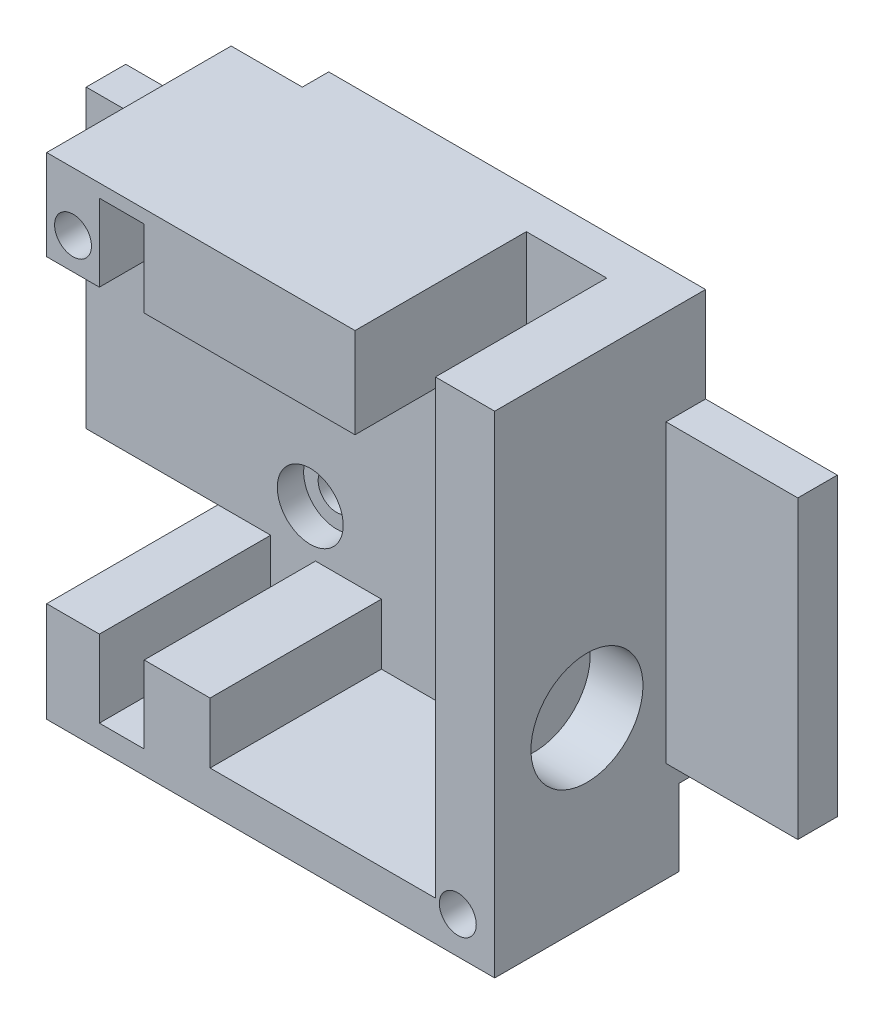
SolidWorks part; units mm, degrees
ref_plane "Front Plane" through (0, 0, 0) normal (0, 0, 1) x (1, 0, 0)
ref_plane "Top Plane" through (0, 0, 0) normal (0, 1, 0) x (1, 0, 0)
ref_plane "Right Plane" through (0, 0, 0) normal (1, 0, 0) x (0, 0, -1)
sketch "Sketch1" plane through (0, 0, 0) normal (0, 0, 1) x (1, 0, 0)
  line L1 (-17, 19) -> (17, 19)
  line L2 (-17, 19) -> (-17, -19)
  line L3 (-17, -19) -> (17, -19)
  line L4 (17, 19) -> (17, -19)
  line L5 (-17, 19) -> (17, -19) construction
  line L6 (-17, -19) -> (17, 19) construction
  point P0 (0, 0)
  dimension "D1" = 38
  dimension "D2" = 34
extrude "Boss-Extrude1" add sketch "Sketch1" along normal blind 16
sketch "Sketch2" plane through (0, 0, 16) normal (0, 0, 1) x (1, 0, 0)
  line L0 (0, 0) -> (-17, 0) construction
  line L5 (-17, 11.4) -> (5.4, 11.4)
  line L6 (-17, 11.4) -> (-17, -11.4)
  line L7 (-17, -11.4) -> (5.4, -11.4)
  line L8 (5.4, 11.4) -> (5.4, -11.4)
  line L9 (-17, 11.4) -> (5.4, -11.4) construction
  line L10 (-17, -11.4) -> (5.4, 11.4) construction
  line L11 (-17, 19) -> (-17, -19) construction
  line L12 (-10.6, -11.4) -> (-10.6, -16.25)
  line L13 (-13, 11.4) -> (-10.6, 11.4)
  line L14 (-13, 11.4) -> (-13, 16.25)
  line L15 (-13, 16.25) -> (-10.6, 16.25)
  line L16 (-10.6, 11.4) -> (-10.6, 16.25)
  line L17 (-13, -11.4) -> (-13, -16.25)
  line L18 (-13, -16.25) -> (-10.6, -16.25)
  line L21 (-17, -11.4) -> (-17, 4.4)
  point P0 (-5.8, 0)
  dimension "D1" = 22.4
  dimension "D2" = 22.8
  dimension "D3" = 5.8
  dimension "D4" = 4
  dimension "D5" = 2.4
  dimension "D6" = 4.85
extrude "Cut-Extrude1" cut sketch "Sketch2" against normal blind 13 contours L8 L5 L6 L7 | L17 L18 L12 L7 | L5 L16 L15 L14
sketch "Sketch3" plane through (0, 0, 16) normal (0, 0, 1) x (1, 0, 0)
  line L1 (5.4, -11.4) -> (-4.6, -11.4)
  line L2 (5.4, -11.4) -> (5.4, -16)
  line L3 (5.4, -16) -> (-4.6, -16)
  line L4 (-4.6, -11.4) -> (-4.6, -16)
  line L5 (5.4, -16) -> (8.4, -16)
  line L6 (5.4, -16) -> (5.4, -11.4)
  line L7 (5.4, -11.4) -> (8.4, -11.4)
  line L8 (8.4, -16) -> (8.4, -11.4)
  line L10 (-17, -19) -> (17, -19) construction
  line L11 (17, 19) -> (-17, 19) construction
  line L12 (8.4, -16) -> (11.4, -16)
  line L13 (8.4, -16) -> (8.4, 19)
  line L14 (8.4, 19) -> (11.4, 19)
  line L15 (11.4, -16) -> (11.4, 19)
  line M11 (17, 19) -> (-17, 19)
  line M21 (5.4, -11.4) -> (-10.6, -11.4)
  dimension "D1" = 3
  dimension "D2" = 10
  dimension "D3" = 3
  dimension "D4" = 3
extrude "Cut-Extrude2" cut sketch "Sketch3" against normal blind 13 contours L12 L15 L13 L8 M11 | L4 L3 L2 M21 | L5 L8 L7 L2 region at (0.4, -13.7, 16) region at (6.9, -13.7, 16) region at (9.9, 1.5, 16)
sketch "Sketch4" plane through (0, 0, 16) normal (0, 0, 1) x (1, 0, 0)
  line L0 (-17, 19) -> (-17, 11.4) construction
  line L3 (-17, -19) -> (17, -19) construction
  line L4 (17, -19) -> (17, 19) construction
  line L5 (8.4, 19) -> (-17, 19) construction
  circle A0 centre (-15, 13.8) radius 1.4
  circle A1 centre (14.2, -16.2) radius 1.4
  dimension "D2" = 5.2
  dimension "D3" = 2.8
  dimension "D4" = 2.8
  dimension "D5" = 2.8
  dimension "D6" = 2.8
  dimension "D1" = 2
extrude "Cut-Extrude3" cut sketch "Sketch4" against normal through all
sketch "Sketch5" plane through (0, 0, 0) normal (0, 0, -1) x (-1, 0, 0)
  line L0 (-17, 19) -> (17, 19) construction
  line L1 (18.4, 13.8) -> (11.6, 13.8)
  line L2 (18.4, 13.8) -> (18.4, 19)
  line L3 (18.4, 19) -> (11.6, 19)
  line L4 (11.6, 13.8) -> (11.6, 19)
  line L5 (-17, -19) -> (-17, 19) construction
  line L6 (-14.2, -19.2) -> (-17, -19.2)
  line L7 (-14.2, -19.2) -> (-14.2, -13.2)
  line L8 (-14.2, -13.2) -> (-17, -13.2)
  line L9 (-17, -19.2) -> (-17, -13.2)
  line L11 (-14.2, -19.2) -> (-10.2, -19.2)
  line L12 (-14.2, -19.2) -> (-14.2, -13.2)
  line L13 (-14.2, -13.2) -> (-10.2, -13.2)
  line L14 (-10.2, -19.2) -> (-10.2, -13.2)
  circle A0 centre (15, 13.8) radius 3.4
  circle A1 centre (-14.2, -16.2) radius 3
  circle M1 centre (15, 13.8) radius 1.4
  circle M2 centre (-14.2, -16.2) radius 1.4
  line M3 (-17, 19) -> (-17, -19)
  line M4 (-17, -19) -> (17, -19)
  line M5 (17, -19) -> (17, 19)
  line M6 (17, 19) -> (-17, 19)
  dimension "D1" = 6.8
  dimension "D2" = 6
  dimension "D3" = 4
extrude "Cut-Extrude5" cut sketch "Sketch5" against normal blind 2 contours A1 L7 M4 M2 | L7 A1 L9 M4 M2 | A1 M3 M4 | A1 L8 M3 | L9 A1 | A1 L7 M4 | A1 L9 L6 M4 | L7 A1 M4 | A0 L2 L3 M5 | A0 L4 M5 M6 | A0 L1 M5 M1 | L1 A0 M5 | A0 L1 M5 | L1 A0 M5 M1 | A1 L14 L13 M4 region at (-17.5712, 12.7332, 0) region at (-17.7757, 17.3011, 0) region at (-17.5712, 14.8668, 0) region at (-14.4405, 12.0641, 0) region at (-14.4405, 15.5359, 0) region at (-13.9912, 17.7377, 0) region at (11.1092, -15.9933, 0) region at (12.7237, -16.1618, 0) region at (13.7943, -19.0802, 0) region at (16.3521, -13.7212, 0) region at (14.6057, -19.0802, 0) region at (15.9461, -19.1069, 0) region at (15.6381, -16.1608, 0) region at (17.0802, -16.2, 0) region at (16.5111, -18.5111, 0)
sketch "Sketch7" plane through (0, 19, 0) normal (0, 1, 0) x (1, 0, 0)
  line L0 (17, -16) -> (17, 0) construction
  line L1 (-17, -16) -> (17, -16)
  line L2 (-17, -16) -> (-17, -15)
  line L3 (-17, -15) -> (17, -15)
  line L4 (17, -16) -> (17, -15)
  dimension "D1" = 1
extrude "Cut-Extrude6" cut sketch "Sketch7" against normal through all
sketch "Sketch9" plane through (0, 0, 15) normal (0, 0, 1) x (1, 0, 0)
  line L0 (8.4, 19) -> (-17, 19) construction
  line L1 (-9, 19) -> (17, 19)
  line L2 (-9, 19) -> (-9, 12.5)
  line L3 (-9, 12.5) -> (17, 12.5)
  line L4 (17, 19) -> (17, 12.5)
  line L5 (17, -19) -> (17, 19) construction
  line L6 (-17, -19) -> (-17, -11.4) construction
  line L7 (-17, -12.4) -> (-14, -12.4)
  line L8 (-17, -12.4) -> (-17, -19)
  line L9 (-17, -19) -> (-14, -19)
  line L10 (-14, -12.4) -> (-14, -19)
  line L11 (17, -19) -> (-17, -19) construction
  line L12 (-13, -16.25) -> (-10.6, -16.25) construction
  line L13 (-8.6, -19) -> (-5.6, -19)
  line L14 (-8.6, -19) -> (-8.6, -12.4)
  line L15 (-8.6, -12.4) -> (-5.6, -12.4)
  line L16 (-5.6, -19) -> (-5.6, -12.4)
  line L17 (-5.6, -19) -> (11.4, -19)
  line L18 (-5.6, -19) -> (-5.6, -17)
  line L19 (-5.6, -17) -> (11.4, -17)
  line L20 (11.4, -19) -> (11.4, -17)
  line L21 (-14, -19) -> (-8.6, -19)
  line L22 (-14, -19) -> (-14, -18.25)
  line L23 (-10.6, -11.4) -> (-4.6, -11.4) construction
  line L24 (-17, -11.4) -> (-13, -11.4) construction
  line L25 (-10.6, -11.4) -> (-10.6, -16.25) construction
  line L26 (-4.6, -11.4) -> (-4.6, -16) construction
  line L27 (-4.6, -16) -> (11.4, -16) construction
  line L28 (-13, -11.4) -> (-13, -16.25) construction
  line L29 (-14, -18.25) -> (-8.6, -18.25)
  line L30 (-8.6, -19) -> (-8.6, -18.25)
  line L32 (-13, 16.25) -> (-10.6, 16.25) construction
  line L33 (-17, 19) -> (-9, 19)
  line L34 (-17, 19) -> (-17, 18.25)
  line L35 (-17, 18.25) -> (-9, 18.25)
  line L36 (-9, 19) -> (-9, 18.25)
  line L37 (11.4, -16) -> (11.4, 19) construction
  line L38 (17, 19) -> (13.4, 19)
  line L39 (17, 19) -> (17, 1)
  line L40 (17, 1) -> (13.4, 1)
  line L41 (13.4, 19) -> (13.4, 1)
  line M21 (8.4, -11.4) -> (8.4, 19)
  line M22 (8.4, 19) -> (-17, 19)
  line M23 (-17, 19) -> (-17, 11.4)
  dimension "D1" = 6.5
  dimension "D2" = 26
  dimension "D3" = 1
  dimension "D4" = 1
  dimension "D5" = 2
  dimension "D6" = 1
  dimension "D7" = 1
  dimension "D8" = 1
  dimension "D9" = 2
  dimension "D10" = 2
  dimension "D11" = 2
  dimension "D12" = 17
  dimension "D13" = 18
extrude "Cut-Extrude9" cut sketch "Sketch9" against normal through all contours L2 L3 M21 M22 | L35 L2 M23 M22 | L41 L1 L3 M21 | L1 L41 L3 L4 | L3 L41 L40 L39 | L17 L20 L19 L16 | L13 L16 L15 L14 | L29 L10 L21 L14 | L10 L7 L8 L9 region at (-0.3, 15.75, 15) region at (-13, 18.625, 15) region at (10.9, 15.75, 15) region at (15.2, 15.75, 15) region at (15.2, 6.75, 15) region at (-15.5, -15.7, 15) region at (-11.3, -18.625, 15) region at (-7.1, -15.7, 15) region at (2.9, -18, 15)
sketch "Sketch10" plane through (0, 0, 3) normal (0, 0, 1) x (1, 0, 0)
  line L1 (-10, 8) -> (10, 8)
  line L2 (-10, 8) -> (-10, -8)
  line L3 (-10, -8) -> (10, -8)
  line L4 (10, 8) -> (10, -8)
  line L5 (-10, 8) -> (10, -8) construction
  line L6 (-10, -8) -> (10, 8) construction
  circle A0 centre (-10, 8) radius 2.5
  circle A1 centre (10, 8) radius 2.5
  circle A2 centre (-10, -8) radius 2.5
  circle A3 centre (10, -8) radius 2.5
  point P0 (0, 0)
  line M6 (8.4, 12.5) -> (8.4, -11.4)
  line M22 (11.4, -16) -> (11.4, 12.5)
  dimension "D3" = 5
  dimension "D1" = 20
  dimension "D2" = 16
extrude "Cut-Extrude10" cut sketch "Sketch10" against normal blind 2 and the other way through all contours L2 A0 L1 | L1 A0 L2 | A1 L4 L1 M6 | A1 L1 L4 M22 M6 | A1 M22 | A1 L1 M6 | L1 A1 M6 | L3 A2 L2 | L2 A2 L3 | A3 L4 L3 M22 M6 | A3 M22 | L4 A3 L3 M6 | A3 L3 M6 | L3 A3 M6 region at (-10.3537, 8.3537, 3) region at (-8.939, 6.939, 3) region at (8.0338, 8.7415, 3) region at (8.0338, 7.2585, 3) region at (-8.939, -6.939, 3) region at (-10.3537, -8.3537, 3) region at (10.1596, 8.4183, 3) region at (9.2324, 6.8354, 3) region at (11.8495, 8, 3) region at (8.0338, -7.2585, 3) region at (9.2324, -6.8354, 3) region at (8.0338, -8.7415, 3) region at (10.1596, -8.4183, 3) region at (11.8495, -8, 3)
sketch "Sketch11" plane through (0, 0, 15) normal (0, 0, 1) x (1, 0, 0)
  line L5 (5.4, -11.4) -> (8.4, -11.4) construction
  line L6 (12.5, -8) -> (7.5, -8)
  line L7 (12.5, -8) -> (12.5, -11.4)
  line L8 (11.4, -11.4) -> (7.5, -11.4)
  line L9 (7.5, -8) -> (7.5, -11.4)
  line L10 (-9, 12.5) -> (8.4, 12.5) construction
  line L11 (12.5, 8) -> (7.5, 8)
  line L12 (12.5, 8) -> (12.5, 12.5)
  line L13 (12.5, 12.5) -> (7.5, 12.5)
  line L14 (7.5, 8) -> (7.5, 12.5)
  line L16 (11.4, -16) -> (12.5, -16)
  line L17 (11.4, -16) -> (11.4, -11.4)
  line L19 (12.5, -16) -> (12.5, -11.4)
  arc A0 (11.4, -10.0712) -> (11.4, -5.9288) centre (10, -8) ccw construction
  arc A1 (11.4, 5.9288) -> (11.4, 10.0712) centre (10, 8) ccw construction
extrude "Cut-Extrude11" cut sketch "Sketch11" against normal blind 12
sketch "Sketch12" plane through (0, 0, 15) normal (0, 0, 1) x (1, 0, 0)
  line L1 (-10.6, 11.4) -> (-9.6, 11.4)
  line L2 (-10.6, 11.4) -> (-10.6, 16.25)
  line L3 (-10.6, 16.25) -> (-9.6, 16.25)
  line L4 (-9.6, 11.4) -> (-9.6, 16.25)
  line L5 (-10.6, -11.4) -> (-9.6, -11.4)
  line L6 (-10.6, -11.4) -> (-10.6, -16.25)
  line L7 (-10.6, -16.25) -> (-9.6, -16.25)
  line L8 (-9.6, -11.4) -> (-9.6, -16.25)
  line L10 (5.4, -11.4) -> (6.4, -11.4)
  line L11 (5.4, -11.4) -> (5.4, 11.4)
  line L12 (5.4, 11.4) -> (6.4, 11.4)
  line L13 (6.4, -11.4) -> (6.4, 11.4)
  dimension "D1" = 1
  dimension "D2" = 1
  dimension "D3" = 4.85
  dimension "D4" = 4.85
  dimension "D5" = 1
extrude "Cut-Extrude12" cut sketch "Sketch12" against normal blind 12
sketch "Sketch14" plane through (17, 0, 0) normal (1, 0, 0) x (0, 0, -1)
  line L0 (-15, -19) -> (-15, 1) construction
  line L1 (-15, -19) -> (-2, -19) construction
  circle A0 centre (-9, -5.4) radius 4.25
  dimension "D1" = 8.5
  dimension "D2" = 6
  dimension "D3" = 13.6
extrude "Cut-Extrude13" cut sketch "Sketch14" against normal blind 4
sketch "Sketch17" plane through (0, 0, 15) normal (0, 0, 1) x (1, 0, 0)
  line L1 (-13, 16.25) -> (-9.6, 16.25)
  line L2 (-13, 16.25) -> (-13, 17.25)
  line L3 (-13, 17.25) -> (-9.6, 17.25)
  line L4 (-9.6, 16.25) -> (-9.6, 17.25)
  line L7 (-9.6, -16.25) -> (-13, -16.25)
  line L8 (-9.6, -16.25) -> (-9.6, -17.25)
  line L9 (-9.6, -17.25) -> (-13, -17.25)
  line L10 (-13, -16.25) -> (-13, -17.25)
  dimension "D1" = 1
  dimension "D2" = 3.4
  dimension "D3" = 1
  dimension "D4" = 3.4
extrude "Cut-Extrude16" cut sketch "Sketch17" against normal blind 12
sketch "Sketch18" plane through (0, 0, 1) normal (0, 0, 1) x (1, 0, 0)
  circle A1 centre (-10, 8) radius 1.4
  circle A2 centre (10, 8) radius 1.4
  circle A3 centre (-10, -8) radius 1.4
  circle A4 centre (10, -8) radius 1.4
  dimension "D1" = 2.8
  dimension "D2" = 2.8
  dimension "D3" = 2.8
  dimension "D4" = 2.8
extrude "Cut-Extrude17" cut sketch "Sketch18" against normal blind 12
sketch "Sketch19" plane through (0, 0, 0) normal (0, 0, 1) x (1, 0, 0)
  line L1 (-17, 18.25) -> (17, 18.25)
  line L2 (-17, 18.25) -> (-17, -19)
  line L3 (-17, -19) -> (17, -19)
  line L4 (17, 18.25) -> (17, -19)
  line L5 (-9, 18.25) -> (17, 18.25)
  line L6 (-9, 18.25) -> (-9, 12.4767)
  line L7 (-9, 12.4767) -> (17, 12.4767)
  line L8 (17, 18.25) -> (17, 12.4767)
  line L9 (17, 12.4767) -> (13.4, 12.4767)
  line L10 (17, 12.4767) -> (17, 1)
  line L11 (17, 1) -> (13.4, 1)
  line L12 (13.4, 12.4767) -> (13.4, 1)
  line L13 (-17, -12.4) -> (-14, -12.4)
  line L14 (-17, -12.4) -> (-17, -19)
  line L15 (-17, -19) -> (-14, -19)
  line L16 (-14, -12.4) -> (-14, -19)
  line L17 (-14, -19) -> (-8.6, -19)
  line L18 (-14, -19) -> (-14, -18.25)
  line L19 (-14, -18.25) -> (-8.6, -18.25)
  line L20 (-8.6, -19) -> (-8.6, -18.25)
  line L21 (-8.6, -12.4) -> (-5.6, -12.4)
  line L22 (-8.6, -12.4) -> (-8.6, -19)
  line L23 (-8.6, -19) -> (-5.6, -19)
  line L24 (-5.6, -12.4) -> (-5.6, -19)
  line L25 (-5.6, -17) -> (11.4, -17)
  line L26 (-5.6, -17) -> (-5.6, -19)
  line L27 (-5.6, -19) -> (11.4, -19)
  line L28 (11.4, -17) -> (11.4, -19)
extrude "Boss-Extrude2" add sketch "Sketch19" along normal blind 16 contours L6 L7 L4 L1 | L7 L12 L11 L4 | L24 L21 L22 L20 L3 | L16 L13 L2 L3 | L3 L20 L19 L16 | L28 L25 L24 L3 region at (4, 15.3633, 0) region at (-15.5, -15.7, 0) region at (15.2, 6.7383, 0) region at (-11.3, -18.625, 0) region at (-7.1, -15.7, 0) region at (2.9, -18, 0)
sketch "Sketch20" plane through (0, 0, 15) normal (0, 0, 1) x (1, 0, 0)
  line L0 (-9.6, 11.4) -> (6.4, 11.4) construction
  line L1 (-17, 18.25) -> (17, 18.25)
  line L2 (-17, 18.25) -> (-17, -19)
  line L3 (-17, -19) -> (17, -19)
  line L4 (17, 18.25) -> (17, -19)
  line L5 (-13, 11.4) -> (-17, 11.4)
  line L6 (-13, 11.4) -> (-13, 18.25)
  line L7 (-13, 18.25) -> (-17, 18.25)
  line L8 (-17, 11.4) -> (-17, 18.25)
  line L9 (-13, 18.25) -> (-9.6, 18.25)
  line L10 (-13, 18.25) -> (-13, 17.25)
  line L11 (-13, 17.25) -> (-9.6, 17.25)
  line L12 (-9.6, 18.25) -> (-9.6, 17.25)
  line L13 (-9.6, 18.25) -> (-9, 18.25)
  line L14 (-9.6, 18.25) -> (-9.6, 11.4)
  line L15 (-9.6, 11.4) -> (-9, 11.4)
  line L16 (-9, 18.25) -> (-9, 11.4)
  line L17 (-17, -11.4) -> (-13, -11.4)
  line L18 (-9, 11.4) -> (7.5, 11.4)
  line L19 (-9, 11.4) -> (-9, 12.4767)
  line L20 (-9, 12.4767) -> (7.5, 12.4767)
  line L21 (7.5, 11.4) -> (7.5, 12.4767)
  line L22 (7.5, -11.4) -> (6.4, -11.4)
  line L23 (7.5, -11.4) -> (7.5, 11.4)
  line L24 (7.5, 11.4) -> (6.4, 11.4)
  line L25 (6.4, -11.4) -> (6.4, 11.4)
  line L26 (17, -19) -> (13.4, -19)
  line L27 (17, -19) -> (17, 1)
  line L28 (17, 1) -> (13.4, 1)
  line L30 (-13, -11.4) -> (-13, -17.25)
  line L31 (-13, -17.25) -> (-9.6, -17.25)
  line L32 (-9.6, -17.25) -> (-9.6, -11.4)
  line L33 (-9.6, -11.4) -> (-4.6, -11.4)
  line L34 (-4.6, -11.4) -> (-4.6, -16)
  line L35 (-4.6, -16) -> (12.5, -16)
  line L36 (12.5, -16) -> (12.5, 12.4767)
  line L37 (12.5, 12.4767) -> (13.4, 12.4767)
  line L38 (13.4, 12.4767) -> (13.4, 1)
  line L39 (-17, -12.4) -> (-14, -12.4)
  line L40 (-14, -12.4) -> (-14, -18.25)
  line L41 (-14, -18.25) -> (-8.6, -18.25)
  line L42 (-8.6, -18.25) -> (-8.6, -12.4)
  line L43 (-8.6, -12.4) -> (-5.6, -12.4)
  line L44 (-5.6, -12.4) -> (-5.6, -17)
  line L45 (-5.6, -17) -> (11.4, -17)
  line L46 (11.4, -17) -> (11.4, -19)
  line L47 (11.4, -19) -> (17, -19)
  circle A0 centre (-15, 13.8) radius 1.4
  circle A1 centre (14.2, -16.2) radius 1.4
  circle M5 centre (-15, 13.8) radius 1.4
  line M6 (7.5, 12.4767) -> (-9, 12.4767)
  line M7 (-9, 12.4767) -> (-9, 18.25)
  line M8 (-9, 18.25) -> (-17, 18.25)
  line M9 (-17, 18.25) -> (-17, 11.4)
  line M10 (-17, 11.4) -> (-13, 11.4)
  line M11 (-13, 11.4) -> (-13, 17.25)
  line M12 (-13, 17.25) -> (-9.6, 17.25)
  line M13 (-9.6, 17.25) -> (-9.6, 11.4)
  line M14 (-9.6, 11.4) -> (6.4, 11.4)
  line M15 (6.4, 11.4) -> (6.4, -11.4)
  line M16 (6.4, -11.4) -> (7.5, -11.4)
  line M17 (7.5, -11.4) -> (7.5, -8)
  line M21 (7.5, 8) -> (7.5, 12.4767)
extrude "Boss-Extrude3" add sketch "Sketch20" along normal blind 1 contours L6 L1 M11 M9 M10 M5 | L12 L1 L6 M12 | L16 L12 M7 M8 M13 M14 | L18 L16 M14 M21 M6 | L23 L18 M17 M21 M15 M16 | L45 L46 L3 L4 L28 L38 L37 L36 L35 L34 L33 L32 L31 L30 L17 L2 L39 L40 L41 L42 L43 L44 A1 region at (-15, 18.1707, 15) region at (-11.3, 17.75, 15) region at (-9.3, 14.825, 15) region at (-15, -11.8633, 15) region at (-0.75, 11.9383, 15) region at (6.95, 0, 15)
sketch "Sketch21" plane through (0, 0, 16) normal (0, 0, 1) x (1, 0, 0)
  line L0 (12.5, -16) -> (12.5, -8) construction
  line L1 (7.5, 12.4767) -> (6.4, 12.4767)
  line L2 (7.5, 12.4767) -> (7.5, -11.4)
  line L3 (7.5, -11.4) -> (6.4, -11.4)
  line L4 (6.4, 12.4767) -> (6.4, -11.4)
  line L5 (7.5, 12.4767) -> (12.5, 12.4767)
  line L6 (7.5, 12.4767) -> (7.5, -11.4)
  line L7 (7.5, -11.4) -> (12.5, -11.4)
  line L8 (12.5, 12.4767) -> (12.5, -11.4)
  line M13 (6.4, 11.4) -> (6.4, -11.4)
  line M14 (6.4, -11.4) -> (7.5, -11.4)
  line M15 (7.5, -11.4) -> (7.5, 12.4767)
  line M16 (7.5, 12.4767) -> (12.5, 12.4767)
  line M17 (12.5, 12.4767) -> (12.5, -16)
extrude "Cut-Extrude18" cut sketch "Sketch21" against normal blind 13 contours L7 M15 M17 M16 | L1 L4 M13 M14 M15 region at (6.95, 0.5383, 16) region at (10, 0.5383, 16)
sketch "Sketch22" plane through (-17, 0, 0) normal (-1, 0, 0) x (0, 0, 1)
  line L0 (3, -11.4) -> (16, -11.4) construction
  line L1 (16, 18.25) -> (0, 18.25)
  line L2 (16, 18.25) -> (16, -19)
  line L3 (16, -19) -> (0, -19)
  line L4 (0, 18.25) -> (0, -19)
  line L5 (0, 11.0505) -> (3, 11.0505)
  line L6 (0, 11.0505) -> (0, -11.4)
  line L7 (0, -11.4) -> (3, -11.4)
  line L8 (3, 11.0505) -> (3, -11.4)
  line L9 (3, 11.4) -> (3, -11.4) construction
  line M3 (3, -11.4) -> (3, 11.4)
  line M8 (2, 11.0505) -> (0, 11.0505)
  line M9 (0, 11.0505) -> (0, -19)
extrude "Boss-Extrude4" add sketch "Sketch22" along normal blind 10 contours L7 L5 M9 M3 M8 region at (-17, -0.1748, 1.5)
ref_plane "Plane1" through (0, 0, 0) normal (1, 0, 0) x (0, 0, -1)
mirror "Mirror1" about plane through (0, 0, 0) normal (1, 0, 0) of "Boss-Extrude4"
sketch "Sketch23" plane through (0, 0, 16) normal (0, 0, 1) x (1, 0, 0)
  line L0 (-17, 18.25) -> (17, 18.25) construction
  line L1 (6.4, 11.4) -> (12.5, 11.4)
  line L2 (6.4, 11.4) -> (6.4, 18.25)
  line L3 (6.4, 18.25) -> (12.5, 18.25)
  line L4 (12.5, 11.4) -> (12.5, 18.25)
extrude "Cut-Extrude19" cut sketch "Sketch23" against normal blind 13
